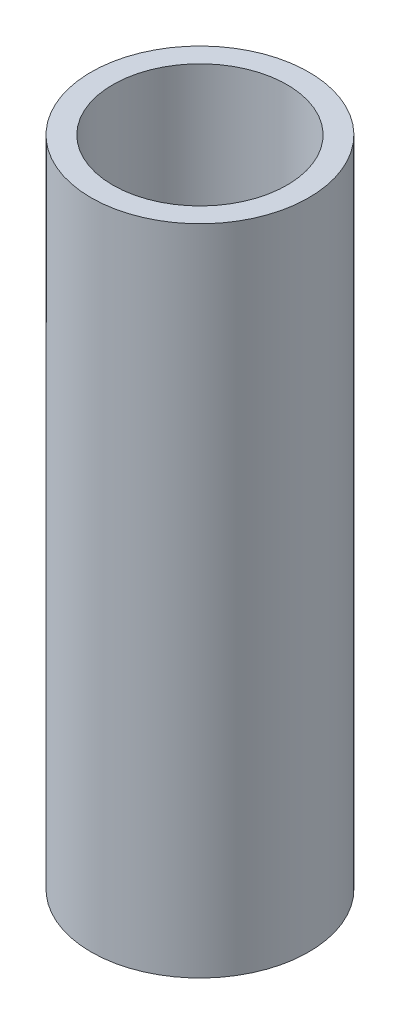
SolidWorks part; units mm, degrees
ref_plane "前视基准面" through (0, 0, 0) normal (0, 0, 1) x (1, 0, 0)
ref_plane "上视基准面" through (0, 0, 0) normal (0, 1, 0) x (1, 0, 0)
ref_plane "右视基准面" through (0, 0, 0) normal (1, 0, 0) x (0, 0, -1)
other "Configuration Table"
sketch "草图1" plane through (0, 0, 0) normal (0, 1, 0) x (1, 0, 0)
  circle A0 centre (0, 0) radius 4
  circle A1 centre (0, 0) radius 5
  dimension "D1" = 1
  dimension "D2" = 10
extrude "凸台-拉伸3" add sketch "草图1" along normal mid plane 30 contours A1
extrude "切除-拉伸1" cut sketch "草图1<10>" along normal through all both and the other way through all contours A0
sketch "草图1<10>" plane through (0, 0, 0) normal (0, 1, 0) x (1, 0, 0) same geometry as "草图1"
